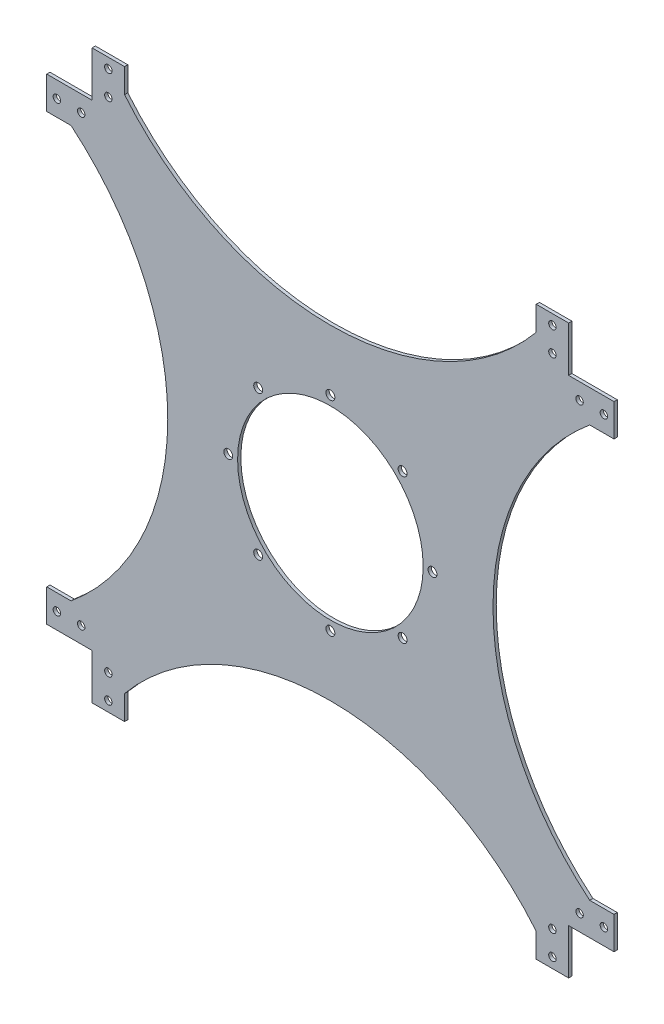
SolidWorks part; units mm, degrees
ref_plane "Front Plane" through (0, 0, 0) normal (0, 0, 1) x (1, 0, 0)
ref_plane "Top Plane" through (0, 0, 0) normal (0, 1, 0) x (1, 0, 0)
ref_plane "Right Plane" through (0, 0, 0) normal (1, 0, 0) x (0, 0, -1)
sketch "Sketch1" plane through (0, 0, 0) normal (0, 0, 1) x (1, 0, 0)
  line L0 (0, 0) -> (367.2182, 0) construction
  line L1 (0, 0) -> (0, -316.5866) construction
  line L2 (0, 0) -> (294, 294) construction
  line L3 (0, 0) -> (294, -294) construction
  line L4 (294, 294) -> (294, 350)
  line L5 (294, 294) -> (350, 294)
  line L6 (294, 350) -> (254, 350)
  line L7 (254, 350) -> (254, 320)
  line L8 (0, 0) -> (-294, 294) construction
  line L9 (0, 0) -> (-294, -294) construction
  line L10 (0, 0) -> (-199.7109, 0) construction
  line L11 (-294, 294) -> (-294, 350)
  line L12 (-294, 350) -> (-254, 350)
  line L13 (-254, 350) -> (-254, 320)
  line L14 (294, -294) -> (350, -294)
  line L15 (350, -294) -> (350, -254)
  line L16 (350, -254) -> (320, -254)
  line L17 (350, 294) -> (350, 254)
  line L18 (350, 254) -> (320, 254)
  line L19 (294, -294) -> (294, -350)
  line L20 (294, -350) -> (254, -350)
  line L21 (254, -350) -> (254, -320)
  line L22 (-254, -350) -> (-254, -320)
  line L23 (-294, -350) -> (-254, -350)
  line L24 (-294, -294) -> (-294, -350)
  line L25 (-294, -294) -> (-350, -294)
  line L26 (-350, -294) -> (-350, -254)
  line L27 (-350, -254) -> (-320, -254)
  line L28 (-350, 254) -> (-320, 254)
  line L29 (-350, 294) -> (-350, 254)
  line L30 (-294, 294) -> (-350, 294)
  circle A0 centre (0, 0) radius 114.5
  arc A1 (-254, 320) -> (254, 320) centre (0, 530.6751) ccw
  arc A2 (320, 254) -> (320, -254) centre (530.6751, 0) ccw
  arc A3 (-254, -320) -> (254, -320) centre (0, -530.6751) cw
  arc A4 (-320, 254) -> (-320, -254) centre (-530.6751, 0) cw
  dimension "D4" = 229
  dimension "D9" = 330
  dimension "D1" = 45
  dimension "D2" = 700
  dimension "D3" = 56
  dimension "D5" = 40
  dimension "D6" = 45
  dimension "D7" = 45
  dimension "D8" = 30
  dimension "D10" = 350
sheet metal parameters "Sheet-Metal1" thickness 4 parameters "D1"=1
base flange "Base-Flange1" sketch "Sketch1" thickness 4 reverse thickness direction yes parameters "D1"=1
sketch "Sketch2" plane through (0, 0, 4) normal (0, 0, 1) x (1, 0, 0)
  line L0 (294, 294) -> (294, 350) construction
  line L1 (294, 350) -> (254, 350) construction
  line L2 (350, 254) -> (350, 294) construction
  line L3 (350, 294) -> (294, 294) construction
  line L4 (0, 0) -> (260.8486, 0) construction
  line L5 (0, 0) -> (0, -250.4708) construction
  circle A0 centre (274, 337.5) radius 4.6
  circle A1 centre (274, 307.5) radius 4.6
  circle A2 centre (307.5, 274) radius 4.6
  circle A3 centre (337.5, 274) radius 4.6
  circle A4 centre (337.5, -274) radius 4.6
  circle A5 centre (307.5, -274) radius 4.6
  circle A6 centre (274, -307.5) radius 4.6
  circle A7 centre (274, -337.5) radius 4.6
  circle A8 centre (-274, -337.5) radius 4.6
  circle A9 centre (-274, -307.5) radius 4.6
  circle A10 centre (-307.5, -274) radius 4.6
  circle A11 centre (-337.5, -274) radius 4.6
  circle A12 centre (-337.5, 274) radius 4.6
  circle A13 centre (-307.5, 274) radius 4.6
  circle A14 centre (-274, 307.5) radius 4.6
  circle A15 centre (-274, 337.5) radius 4.6
  point P8 (294, 322)
  dimension "D2" = 9.2
  dimension "D1" = 20
  dimension "D3" = 12.5
  dimension "D4" = 30
  dimension "D5" = 30
  dimension "D6" = 12.5
  dimension "D7" = 20
extrude "Extrude1" cut sketch "Sketch2" against normal blind 4 normal cut yes
sketch "Sketch3" plane through (0, 0, 4) normal (0, 0, 1) x (1, 0, 0)
  line L0 (0, 0) -> (220.4396, 0) construction
  line L1 (0, 0) -> (0, -219.5819) construction
  line L2 (0, 0) -> (178.1909, 178.1909) construction
  circle A0 centre (0, 0) radius 126 construction
  circle A1 centre (0, 126) radius 5.5
  circle A2 centre (-126, 0) radius 5.5 construction
  circle A3 centre (0, -126) radius 5.5 construction
  circle A4 centre (126, 0) radius 5.5 construction
  dimension "D2" = 11
  dimension "D3" = 252
  dimension "D1" = 45
extrude "Extrude2" cut sketch "Sketch3" against normal blind 4 normal cut yes
pattern_circular "CirPattern1" count 8 every 45 about axis through (0, 0, 4) along (0, 0, 1) of "Extrude2"
flat pattern "Flat-Pattern1" [suppressed]
sketch "Bend-Lines1" plane through (0, 0, 0) normal (0, 1, 0) x (-1, 0, 0)
